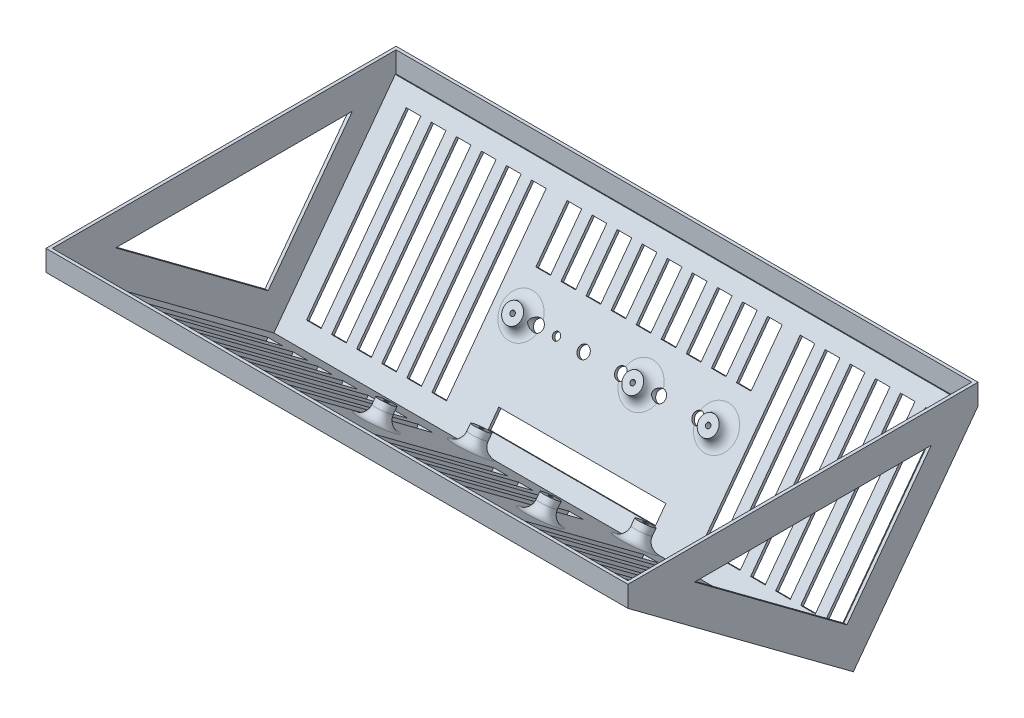
SolidWorks part; units mm, degrees
ref_plane "Front" through (0, 0, 0) normal (0, 0, 1) x (1, 0, 0)
ref_plane "Top" through (0, 0, 0) normal (0, 1, 0) x (1, 0, 0)
ref_plane "Right" through (0, 0, 0) normal (1, 0, 0) x (0, 0, -1)
sketch "Sketch1" plane through (0, 0, 0) normal (0, 1, 0) x (1, 0, 0)
  line L0 (1.7, -169.3) -> (280.3, -169.3)
  line L1 (0, 0) -> (282, 0)
  line L2 (0, 0) -> (0, -171)
  line L3 (0, -171) -> (282, -171)
  line L4 (282, 0) -> (282, -171)
  line L5 (280.3, -1.7) -> (280.3, -169.3)
  line L6 (1.7, -1.7) -> (280.3, -1.7)
  line L7 (1.7, -1.7) -> (1.7, -169.3)
  line L8 (0.2, -0.2) -> (0.2, -170.8)
  line L9 (0.2, -170.8) -> (281.8, -170.8)
  line L10 (281.8, -0.2) -> (281.8, -170.8)
  line L11 (0.2, -0.2) -> (281.8, -0.2)
  line L12 (3.2, -3.2) -> (3.2, -167.8)
  line L13 (3.2, -167.8) -> (278.8, -167.8)
  line L14 (278.8, -3.2) -> (278.8, -167.8)
  line L15 (3.2, -3.2) -> (278.8, -3.2)
  dimension "D1" = 171
  dimension "D2" = 282
  dimension "D3" = 1.7
  dimension "D4" = 1.5
  dimension "D5" = 1.5
extrude "Boss-Extrude2" add sketch "Sketch1" along normal blind 10 contours L6 L7 L0 L5 L12 L15 L14 L13
sketch "Sketch2" plane through (280.3, 0, 0) normal (1, 0, 0) x (0, 0, -1)
  line L0 (-1.7, 0) -> (-61.3644, -80.2506)
  line L1 (-61.3644, -80.2506) -> (-169.3, 0)
  line L2 (-169.3, 0) -> (-1.7, 0)
  dimension "D1" = 100
  dimension "D2" = 134.5
extrude "Boss-Extrude3" add sketch "Sketch2" against normal blind 1.5
sketch "Sketch3" plane through (278.8, 0, 0) normal (-1, 0, 0) x (0, 0, 1)
  line L0 (61.3644, -80.2506) -> (1.7, 0)
  line L1 (61.3644, -80.2506) -> (62.5682, -79.3556)
  line L2 (169.3, 0) -> (61.3644, -80.2506) construction
  line L3 (61.6732, -78.1519) -> (3.5669, 0)
  line L4 (3.5669, 0) -> (1.7, 0)
  line L5 (62.5682, -79.3556) -> (169.3, 0)
  line L6 (61.6732, -78.1519) -> (166.786, 0)
  line L7 (166.786, 0) -> (169.3, 0)
  dimension "D1" = 1.5
  dimension "D2" = 1.5
extrude "Boss-Extrude4" add sketch "Sketch3" along normal blind 277.1
sketch "Sketch4" plane through (1.7, 0, 0) normal (-1, 0, 0) x (0, 0, 1)
  line L0 (61.6732, -78.1519) -> (3.5669, 0)
  line L1 (61.6732, -78.1519) -> (3.5669, 0) construction
  line L2 (3.5669, 0) -> (166.786, 0)
  line L3 (166.786, 0) -> (61.6732, -78.1519)
extrude "Boss-Extrude5" add sketch "Sketch4" against normal blind 1.5
sketch "Sketch5" plane through (0, -79.8598, 59.3761) normal (0, 0.8025, -0.5967) x (1, 0, 0)
  line L0 (3.2, -2.8624) -> (278.8, -2.8624) construction
  line L1 (3.2, -2.8624) -> (3.2, -133.8449) construction
  circle A0 centre (101.7, -7.8624) radius 4
  circle A1 centre (180.3, -7.8624) radius 4
  circle A2 centre (101.7, -64.4624) radius 4
  circle A3 centre (180.3, -64.4624) radius 4
  dimension "D9" = 8
  dimension "D10" = 8
  dimension "D11" = 8
  dimension "D12" = 8
  dimension "D1" = 5
  dimension "D2" = 5
  dimension "D3" = 61.6
  dimension "D4" = 61.6
  dimension "D5" = 78.6
  dimension "D6" = 78.6
  dimension "D7" = 98.5
  dimension "D8" = 98.5
extrude "Boss-Extrude6" add sketch "Sketch5" along normal blind 8
fillet "Fillet1" radius 5 4 edges at (180.3, -77.5552, 62.4757) (180.3, -43.7843, 107.8969) (101.7, -77.5552, 62.4757) (101.7, -43.7843, 107.8969)
sketch "Sketch7" plane through (0, 1.7079, 2.2971) normal (0, 0.5967, 0.8025) x (1, 0, 0)
  line L0 (109.1833, -99.5143) -> (172.8167, -99.5143) construction
  line L1 (101, -91.5143) -> (181, -91.5143)
  line L2 (101, -91.5143) -> (101, -83.0143)
  line L3 (101, -83.0143) -> (181, -83.0143)
  line L4 (181, -91.5143) -> (181, -83.0143)
  line L6 (3.2, -2.1282) -> (3.2, -99.5143) construction
  dimension "D1" = 8.5
  dimension "D2" = 8
  dimension "D3" = 80
  dimension "D4" = 97.8
extrude "Cut-Extrude1" cut sketch "Sketch7" against normal blind 8
sketch "Sketch8" plane through (0, 1.7079, 2.2971) normal (0, 0.5967, 0.8025) x (1, 0, 0)
  line L0 (3.2, -2.1282) -> (278.8, -2.1282) construction
  line L1 (3.2, -1.9093) -> (278.8, -1.9093) construction
  line L2 (3.2, -2.1282) -> (3.2, -99.5143) construction
  circle A0 centre (93.2, -52.1282) radius 4.5
  circle A1 centre (150.7, -52.1282) radius 4.5
  circle A2 centre (186.7, -51.9093) radius 4.5
  point P10 (0, 0)
  point P11 (0, 0)
  dimension "D1" = 9
  dimension "D2" = 9
  dimension "D3" = 9
  dimension "D4" = 50
  dimension "D5" = 50
  dimension "D6" = 50
  dimension "D7" = 57.5
  dimension "D8" = 36
  dimension "D9" = 90
extrude "Boss-Extrude7" add sketch "Sketch8" along normal blind 5
sketch "Sketch9" plane through (0, 1.7079, 2.2971) normal (0, 0.5967, 0.8025) x (1, 0, 0)
  line L0 (3.2, -2.1282) -> (278.8, -2.1282) construction
  circle A0 centre (101.2, -52.1282) radius 2.75
  circle A1 centre (110.2, -52.1282) radius 1.75
  circle A2 centre (123.2, -52.1282) radius 2.75
  circle A3 centre (141.2, -52.1282) radius 2.75
  circle A4 centre (159.7, -52.1282) radius 2.75
  circle A5 centre (178.2, -52.1282) radius 2.75
  circle A6 centre (93.2, -52.1282) radius 4.5 construction
  circle A8 centre (150.7, -52.1282) radius 4.5 construction
  point P16 (0, 0)
  dimension "D7" = 5.5
  dimension "D8" = 5.5
  dimension "D9" = 5.5
  dimension "D10" = 3.5
  dimension "D11" = 5.5
  dimension "D12" = 5.5
  dimension "D1" = 50
  dimension "D2" = 50
  dimension "D3" = 50
  dimension "D4" = 50
  dimension "D5" = 50
  dimension "D6" = 50
  dimension "D13" = 8
  dimension "D14" = 9
  dimension "D15" = 13
  dimension "D16" = 18
  dimension "D17" = 9
  dimension "D18" = 18.5
extrude "Cut-Extrude2" cut sketch "Sketch9" against normal through all
fillet "Fillet2" radius 5 3 edges at (186.7, -36.3378, 30.5843) (150.7, -36.5135, 30.7149) (93.2, -36.5135, 30.7149)
sketch "Sketch10" plane through (0, -73.4398, 54.6028) normal (0, 0.8025, -0.5967) x (1, 0, 0)
  circle A0 centre (101.7, -64.4624) radius 1.1
  circle A1 centre (180.3, -64.4624) radius 1.1
  circle A2 centre (180.3, -7.8624) radius 1.1
  circle A3 centre (101.7, -7.8624) radius 1.1
  dimension "D1" = 2.2
  dimension "D2" = 2.2
  dimension "D3" = 2.2
  dimension "D4" = 2.2
extrude "Cut-Extrude3" cut sketch "Sketch10" against normal blind 5
sketch "Sketch11" plane through (0, 4.6912, 6.3096) normal (0, 0.5967, 0.8025) x (1, 0, 0)
  circle A0 centre (93.2, -52.1282) radius 1.15
  circle A1 centre (150.7, -52.1282) radius 1.15
  circle A2 centre (186.7, -51.9093) radius 1.15
  dimension "D1" = 2.3
  dimension "D2" = 2.3
  dimension "D3" = 2.3
extrude "Cut-Extrude4" cut sketch "Sketch11" against normal blind 4
sketch "Sketch12" plane through (0, 1.7079, 2.2971) normal (0, 0.5967, 0.8025) x (1, 0, 0)
  line L0 (25.2, -90.1282) -> (25.2, -10.1282)
  line L1 (13.2, -90.1282) -> (20.2, -90.1282)
  line L2 (13.2, -90.1282) -> (13.2, -10.1282)
  line L3 (13.2, -10.1282) -> (20.2, -10.1282)
  line L4 (20.2, -90.1282) -> (20.2, -10.1282)
  line L5 (25.2, -90.1282) -> (32.2, -90.1282)
  line L6 (32.2, -90.1282) -> (32.2, -10.1282)
  line L7 (25.2, -10.1282) -> (32.2, -10.1282)
  line L8 (37.2, -90.1282) -> (37.2, -10.1282)
  line L9 (37.2, -90.1282) -> (44.2, -90.1282)
  line L10 (44.2, -90.1282) -> (44.2, -10.1282)
  line L11 (37.2, -10.1282) -> (44.2, -10.1282)
  line L12 (49.2, -90.1282) -> (49.2, -10.1282)
  line L13 (49.2, -90.1282) -> (56.2, -90.1282)
  line L14 (56.2, -90.1282) -> (56.2, -10.1282)
  line L15 (49.2, -10.1282) -> (56.2, -10.1282)
  line L16 (61.2, -90.1282) -> (61.2, -10.1282)
  line L17 (61.2, -90.1282) -> (68.2, -90.1282)
  line L18 (68.2, -90.1282) -> (68.2, -10.1282)
  line L19 (61.2, -10.1282) -> (68.2, -10.1282)
  line L20 (3.2, -2.1282) -> (3.2, -99.5143) construction
  line L21 (3.2, -2.1282) -> (278.8, -2.1282) construction
  line L22 (73.2, -90.1282) -> (73.2, -10.1282)
  line L23 (73.2, -90.1282) -> (80.2, -90.1282)
  line L24 (80.2, -90.1282) -> (80.2, -10.1282)
  line L25 (73.2, -10.1282) -> (80.2, -10.1282)
  line L26 (141, -2.1282) -> (141, -77.8196) construction
  line L27 (268.8, -90.1282) -> (261.8, -90.1282)
  line L28 (268.8, -10.1282) -> (261.8, -10.1282)
  line L29 (268.8, -90.1282) -> (268.8, -10.1282)
  line L30 (261.8, -90.1282) -> (261.8, -10.1282)
  line L31 (249.8, -90.1282) -> (249.8, -10.1282)
  line L32 (256.8, -90.1282) -> (249.8, -90.1282)
  line L33 (256.8, -90.1282) -> (256.8, -10.1282)
  line L34 (256.8, -10.1282) -> (249.8, -10.1282)
  line L35 (237.8, -90.1282) -> (237.8, -10.1282)
  line L36 (244.8, -90.1282) -> (237.8, -90.1282)
  line L37 (244.8, -90.1282) -> (244.8, -10.1282)
  line L38 (244.8, -10.1282) -> (237.8, -10.1282)
  line L39 (225.8, -90.1282) -> (225.8, -10.1282)
  line L40 (232.8, -90.1282) -> (225.8, -90.1282)
  line L41 (232.8, -90.1282) -> (232.8, -10.1282)
  line L42 (232.8, -10.1282) -> (225.8, -10.1282)
  line L43 (213.8, -90.1282) -> (213.8, -10.1282)
  line L44 (220.8, -90.1282) -> (213.8, -90.1282)
  line L45 (220.8, -90.1282) -> (220.8, -10.1282)
  line L46 (220.8, -10.1282) -> (213.8, -10.1282)
  line L47 (201.8, -90.1282) -> (201.8, -10.1282)
  line L48 (208.8, -90.1282) -> (201.8, -90.1282)
  line L49 (208.8, -90.1282) -> (208.8, -10.1282)
  line L50 (208.8, -10.1282) -> (201.8, -10.1282)
  dimension "D2" = 80
  dimension "D3" = 7
  dimension "D4" = 10
  dimension "D5" = 8
  dimension "D1" = 6
  dimension "D6" = 6
extrude "Cut-Extrude5" cut sketch "Sketch12" against normal through all
sketch "Sketch13" plane through (0, 1.7079, 2.2971) normal (0, 0.5967, 0.8025) x (1, 0, 0)
  line L0 (102.2, -35.1282) -> (102.2, -10.1282)
  line L1 (90.2, -35.1282) -> (97.2, -35.1282)
  line L2 (90.2, -35.1282) -> (90.2, -10.1282)
  line L3 (90.2, -10.1282) -> (97.2, -10.1282)
  line L4 (97.2, -35.1282) -> (97.2, -10.1282)
  line L5 (102.2, -35.1282) -> (109.2, -35.1282)
  line L6 (109.2, -35.1282) -> (109.2, -10.1282)
  line L7 (102.2, -10.1282) -> (109.2, -10.1282)
  line L8 (114.2, -35.1282) -> (114.2, -10.1282)
  line L9 (114.2, -35.1282) -> (121.2, -35.1282)
  line L10 (121.2, -35.1282) -> (121.2, -10.1282)
  line L11 (114.2, -10.1282) -> (121.2, -10.1282)
  line L12 (126.2, -35.1282) -> (126.2, -10.1282)
  line L13 (126.2, -35.1282) -> (133.2, -35.1282)
  line L14 (133.2, -35.1282) -> (133.2, -10.1282)
  line L15 (126.2, -10.1282) -> (133.2, -10.1282)
  line L16 (138.2, -35.1282) -> (138.2, -10.1282)
  line L17 (138.2, -35.1282) -> (145.2, -35.1282)
  line L18 (145.2, -35.1282) -> (145.2, -10.1282)
  line L19 (138.2, -10.1282) -> (145.2, -10.1282)
  line L20 (150.2, -35.1282) -> (150.2, -10.1282)
  line L21 (150.2, -35.1282) -> (157.2, -35.1282)
  line L22 (157.2, -35.1282) -> (157.2, -10.1282)
  line L23 (150.2, -10.1282) -> (157.2, -10.1282)
  line L24 (162.2, -35.1282) -> (162.2, -10.1282)
  line L25 (162.2, -35.1282) -> (169.2, -35.1282)
  line L26 (169.2, -35.1282) -> (169.2, -10.1282)
  line L27 (162.2, -10.1282) -> (169.2, -10.1282)
  line L28 (174.2, -35.1282) -> (174.2, -10.1282)
  line L29 (174.2, -35.1282) -> (181.2, -35.1282)
  line L30 (181.2, -35.1282) -> (181.2, -10.1282)
  line L31 (174.2, -10.1282) -> (181.2, -10.1282)
  line L32 (186.2, -35.1282) -> (186.2, -10.1282)
  line L33 (186.2, -35.1282) -> (193.2, -35.1282)
  line L34 (193.2, -35.1282) -> (193.2, -10.1282)
  line L35 (186.2, -10.1282) -> (193.2, -10.1282)
  dimension "D1" = 25
  dimension "D2" = 7
  dimension "D3" = 0
  dimension "D4" = 10
  dimension "D5" = 9
extrude "Cut-Extrude6" cut sketch "Sketch13" against normal blind 5
sketch "Sketch14" plane through (0, -79.8598, 59.3761) normal (0, 0.8025, -0.5967) x (1, 0, 0)
  line L0 (3.2, -2.8624) -> (3.2, -133.8449) construction
  line L1 (13.2, -18.8449) -> (20.2, -18.8449)
  line L2 (13.2, -18.8449) -> (13.2, -118.8449)
  line L3 (13.2, -118.8449) -> (20.2, -118.8449)
  line L4 (20.2, -18.8449) -> (20.2, -118.8449)
  line L5 (3.2, -133.8449) -> (278.8, -133.8449) construction
  line L6 (25.2, -18.8449) -> (25.2, -118.8449)
  line L7 (25.2, -118.8449) -> (32.2, -118.8449)
  line L8 (32.2, -18.8449) -> (32.2, -118.8449)
  line L9 (25.2, -18.8449) -> (32.2, -18.8449)
  line L10 (37.2, -18.8449) -> (37.2, -118.8449)
  line L11 (37.2, -118.8449) -> (44.2, -118.8449)
  line L12 (44.2, -18.8449) -> (44.2, -118.8449)
  line L13 (37.2, -18.8449) -> (44.2, -18.8449)
  line L14 (49.2, -18.8449) -> (49.2, -118.8449)
  line L15 (49.2, -118.8449) -> (56.2, -118.8449)
  line L16 (56.2, -18.8449) -> (56.2, -118.8449)
  line L17 (49.2, -18.8449) -> (56.2, -18.8449)
  line L18 (61.2, -18.8449) -> (61.2, -118.8449)
  line L19 (61.2, -118.8449) -> (68.2, -118.8449)
  line L20 (68.2, -18.8449) -> (68.2, -118.8449)
  line L21 (61.2, -18.8449) -> (68.2, -18.8449)
  line L22 (73.2, -18.8449) -> (73.2, -118.8449)
  line L23 (73.2, -118.8449) -> (80.2, -118.8449)
  line L24 (80.2, -18.8449) -> (80.2, -118.8449)
  line L25 (73.2, -18.8449) -> (80.2, -18.8449)
  line L26 (85.2, -18.8449) -> (85.2, -118.8449)
  line L27 (85.2, -118.8449) -> (92.2, -118.8449)
  line L28 (92.2, -18.8449) -> (92.2, -118.8449)
  line L29 (85.2, -18.8449) -> (92.2, -18.8449)
  line L38 (121.2, -18.8449) -> (121.2, -118.8449)
  line L39 (121.2, -118.8449) -> (128.2, -118.8449)
  line L40 (128.2, -18.8449) -> (128.2, -118.8449)
  line L41 (121.2, -18.8449) -> (128.2, -18.8449)
  line L42 (133.2, -18.8449) -> (133.2, -118.8449)
  line L43 (133.2, -118.8449) -> (140.2, -118.8449)
  line L44 (140.2, -18.8449) -> (140.2, -118.8449)
  line L45 (133.2, -18.8449) -> (140.2, -18.8449)
  line L46 (145.2, -18.8449) -> (145.2, -118.8449)
  line L47 (145.2, -118.8449) -> (152.2, -118.8449)
  line L48 (152.2, -18.8449) -> (152.2, -118.8449)
  line L49 (145.2, -18.8449) -> (152.2, -18.8449)
  line L50 (157.2, -18.8449) -> (157.2, -118.8449)
  line L51 (157.2, -118.8449) -> (164.2, -118.8449)
  line L52 (164.2, -18.8449) -> (164.2, -118.8449)
  line L53 (157.2, -18.8449) -> (164.2, -18.8449)
  line L62 (193.2, -18.8449) -> (193.2, -118.8449)
  line L63 (193.2, -118.8449) -> (200.2, -118.8449)
  line L64 (200.2, -18.8449) -> (200.2, -118.8449)
  line L65 (193.2, -18.8449) -> (200.2, -18.8449)
  line L66 (205.2, -18.8449) -> (205.2, -118.8449)
  line L67 (205.2, -118.8449) -> (212.2, -118.8449)
  line L68 (212.2, -18.8449) -> (212.2, -118.8449)
  line L69 (205.2, -18.8449) -> (212.2, -18.8449)
  line L70 (217.2, -18.8449) -> (217.2, -118.8449)
  line L71 (217.2, -118.8449) -> (224.2, -118.8449)
  line L72 (224.2, -18.8449) -> (224.2, -118.8449)
  line L73 (217.2, -18.8449) -> (224.2, -18.8449)
  line L74 (229.2, -18.8449) -> (229.2, -118.8449)
  line L75 (229.2, -118.8449) -> (236.2, -118.8449)
  line L76 (236.2, -18.8449) -> (236.2, -118.8449)
  line L77 (229.2, -18.8449) -> (236.2, -18.8449)
  line L78 (241.2, -18.8449) -> (241.2, -118.8449)
  line L79 (241.2, -118.8449) -> (248.2, -118.8449)
  line L80 (248.2, -18.8449) -> (248.2, -118.8449)
  line L81 (241.2, -18.8449) -> (248.2, -18.8449)
  line L82 (253.2, -18.8449) -> (253.2, -118.8449)
  line L83 (253.2, -118.8449) -> (260.2, -118.8449)
  line L84 (260.2, -18.8449) -> (260.2, -118.8449)
  line L85 (253.2, -18.8449) -> (260.2, -18.8449)
  line L86 (265.2, -18.8449) -> (265.2, -118.8449)
  line L87 (265.2, -118.8449) -> (272.2, -118.8449)
  line L88 (272.2, -18.8449) -> (272.2, -118.8449)
  line L89 (265.2, -18.8449) -> (272.2, -18.8449)
  line L92 (97.2, -18.8449) -> (97.2, -118.8449)
  line L93 (104.2, -18.8449) -> (104.2, -118.8449)
  line L94 (97.2, -118.8449) -> (104.2, -118.8449)
  line L95 (97.2, -18.8449) -> (104.2, -18.8449)
  line L96 (181.2, -18.8449) -> (181.2, -118.8449)
  line L97 (181.2, -18.8449) -> (188.2, -18.8449)
  line L98 (188.2, -18.8449) -> (188.2, -118.8449)
  line L99 (181.2, -118.8449) -> (188.2, -118.8449)
  line L100 (176.2, -18.8449) -> (176.2, -118.8449)
  line L101 (169.2, -18.8449) -> (169.2, -118.8449)
  line L102 (169.2, -118.8449) -> (176.2, -118.8449)
  line L103 (169.2, -18.8449) -> (176.2, -18.8449)
  line L104 (109.2, -18.8449) -> (109.2, -118.8449)
  line L105 (109.2, -18.8449) -> (116.2, -18.8449)
  line L106 (116.2, -18.8449) -> (116.2, -118.8449)
  line L107 (109.2, -118.8449) -> (116.2, -118.8449)
  dimension "D1" = 7
  dimension "D2" = 100
  dimension "D3" = 10
  dimension "D4" = 15
  dimension "D5" = 22
extrude "Cut-Extrude7" cut sketch "Sketch14" against normal blind 5
sketch "Sketch15" plane through (280.3, 0, 0) normal (1, 0, 0) x (0, 0, -1)
  line L6 (-24.1088, -5) -> (-137.4351, -5)
  line L8 (-137.4351, -5) -> (-64.4522, -59.2631)
  line L9 (-64.4522, -59.2631) -> (-24.1088, -5)
extrude "Cut-Extrude10" cut sketch "Sketch15" against normal through all
